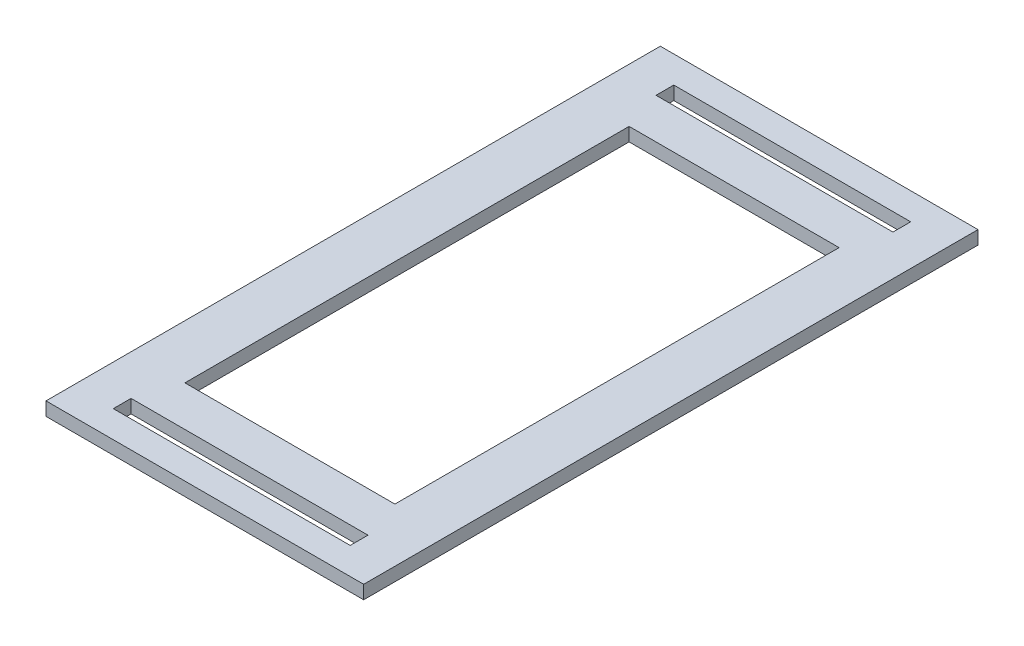
SolidWorks part; units mm, degrees
material "Acrylic (Medium-high impact)"
ref_plane "Front Plane" through (0, 0, 0) normal (0, 0, 1) x (1, 0, 0)
ref_plane "Top Plane" through (0, 0, 0) normal (0, 1, 0) x (1, 0, 0)
ref_plane "Right Plane" through (0, 0, 0) normal (1, 0, 0) x (0, 0, -1)
sketch "Sketch1" plane through (0, 0, 0) normal (0, 1, 0) x (1, 0, 0)
  line L0 (0, 52.3875) -> (0, 0) construction
  line L1 (-37.465, 72.4535) -> (37.465, 72.4535)
  line L2 (-37.465, 72.4535) -> (-37.465, -72.4535)
  line L3 (-37.465, -72.4535) -> (37.465, -72.4535)
  line L4 (37.465, 72.4535) -> (37.465, -72.4535)
  line L5 (-27.94, -61.9125) -> (27.94, -61.9125)
  line L6 (-27.94, -61.9125) -> (-27.94, -66.1035)
  line L7 (-27.94, -66.1035) -> (27.94, -66.1035)
  line L8 (27.94, -61.9125) -> (27.94, -66.1035)
  line L9 (-27.94, 66.1035) -> (27.94, 66.1035)
  line L10 (-27.94, 66.1035) -> (-27.94, 61.9125)
  line L11 (-27.94, 61.9125) -> (27.94, 61.9125)
  line L12 (27.94, 66.1035) -> (27.94, 61.9125)
  line L13 (-24.765, 52.3875) -> (24.765, 52.3875)
  line L14 (-24.765, 52.3875) -> (-24.765, -52.3875)
  line L15 (-24.765, -52.3875) -> (24.765, -52.3875)
  line L16 (24.765, 52.3875) -> (24.765, -52.3875)
  line L17 (-37.465, 0) -> (0, 0) construction
  point P4 (-37.465, 0)
  point P6 (0, 72.4535)
  point P11 (0, -61.9125)
  point P16 (0, 61.9125)
  point P23 (-24.765, 0)
  dimension "D1" = 55.88
  dimension "D2" = 4.191
  dimension "D3" = 6.35
  dimension "D8" = 9.525
  dimension "D4" = 123.825
  dimension "D5" = 6.35
  dimension "D6" = 3.175
  dimension "D7" = 9.525
extrude "Boss-Extrude1" add sketch "Sketch1" along normal blind 3.175
sketch "Sketch2" plane through (0, 3.175, 0) normal (0, 1, 0) x (1, 0, 0)
  line L0 (-37.465, -61.9125) -> (-37.465, 61.9125)
  line L1 (-37.465, 72.4535) -> (-37.465, -72.4535) construction
  line L2 (-19.05, 0) -> (19.05, 0)
  line L3 (37.465, -72.4535) -> (37.465, 72.4535) construction
  line L4 (37.465, -61.9125) -> (37.465, 61.9125)
  line L5 (-1.7462, 0) -> (1.7462, 0) construction
  arc A0 (-37.465, -61.9125) -> (-31.75, -42.6983) centre (-2.3077, -61.9125) cw
  arc A1 (-31.75, -42.6983) -> (-31.75, 42.6983) centre (-97.1773, 0) ccw
  arc A2 (31.75, 42.6983) -> (31.75, -42.6983) centre (97.1773, 0) ccw
  arc A3 (31.75, -42.6983) -> (37.465, -61.9125) centre (2.3077, -61.9125) cw
  arc A4 (31.75, 42.6983) -> (37.465, 61.9125) centre (2.3077, 61.9125) ccw
  arc A5 (-37.465, 61.9125) -> (-31.75, 42.6983) centre (-2.3077, 61.9125) ccw
  point P1 (-28.575, 27.6604)
  point P25 (37.465, 0)
  point P26 (-37.465, 0)
  point P27 (-28.575, -38.6834)
  point P28 (0, 0)
  line M2 (-37.465, 72.4535) -> (-37.465, -72.4535)
  line M4 (37.465, -72.4535) -> (37.465, 72.4535)
  dimension "D2" = 63.5
  dimension "D1" = 38.1
extrude "Cut-Extrude1" [suppressed] cut sketch "Sketch2" against normal through all contours A5 A0 A1 M2 | A4 A2 A3 M4
equation "\"bottomThickness\"= .25in"
equation "\"wallThickness\"= .125in"
equation "\"D2@Sketch1\"=\"wallThickness\"+.04"
equation "\"D1@Boss-Extrude1\"=\"wallThickness\""
